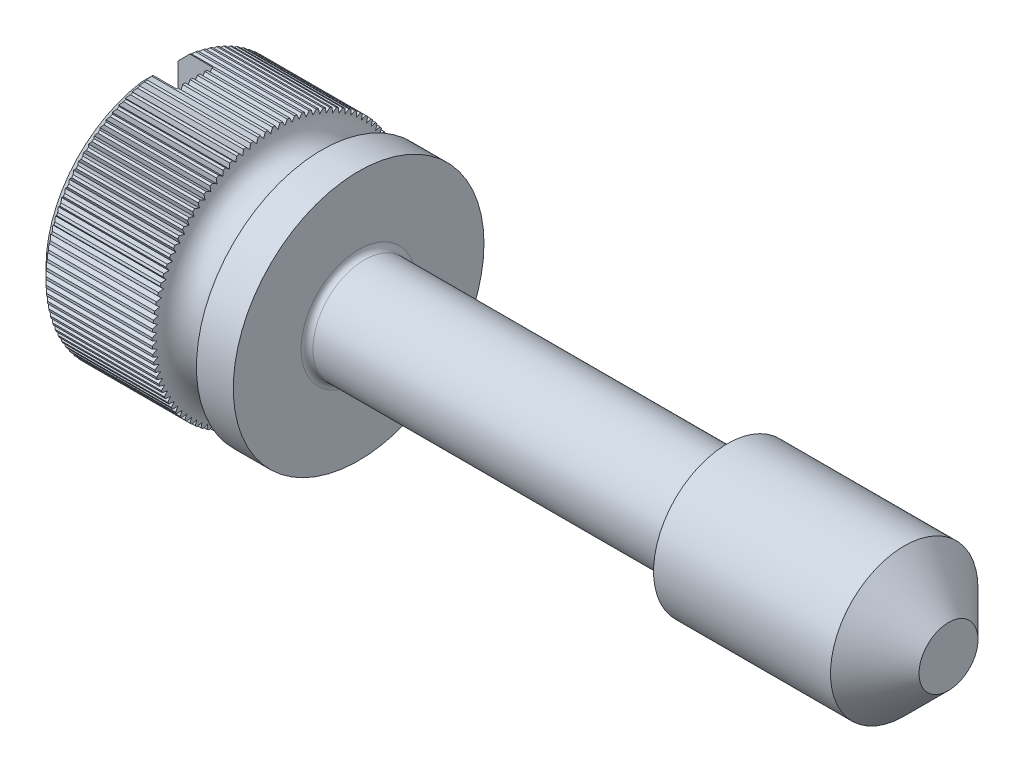
SolidWorks part; units mm, degrees
ref_plane "Front" through (0, 0, 0) normal (0, 0, 1) x (1, 0, 0)
ref_plane "Top" through (0, 0, 0) normal (0, 1, 0) x (1, 0, 0)
ref_plane "Right" through (0, 0, 0) normal (1, 0, 0) x (0, 0, -1)
sketch "Sketch1" plane through (0, 0, 0) normal (1, 0, 0) x (0, 0, -1)
  circle A0 centre (0, 0) radius 8.5
extrude "BaseHead" add sketch "Sketch1" along normal blind 13.5
sketch "Sketch2" plane through (12.6635, 0, 1.1635) normal (0, 1, 0) x (0, 0, 1)
  line L0 (7.3365, -1.6635) -> (10.3365, -1.6635)
  line L1 (7.3365, -4.6635) -> (10.3365, -4.6635)
  line L2 (10.3365, -4.6635) -> (10.3365, -1.6635)
  line L3 (7.3365, -12.6635) -> (7.3365, 0.8365) construction
  line L4 (7.3365, 0.8365) -> (-9.6635, 0.8365) construction
  line L5 (-1.1635, 4.9919) -> (-1.1635, -18.8189) construction
  arc A0 (7.3365, -1.6635) -> (7.3365, -4.6635) centre (7.3365, -3.1635) ccw
  dimension "db" = 3
  dimension "h" = 2.5
  dimension "D3" = 3
revolve "Cut-Revolve1" cut sketch "Sketch2" angle 360 about L5
chamfer "Chamfer1" distance 0.8 angle 45 1 edges at (0, 0, -8.5)
sketch "Sketch3" plane through (0, 0, 0) normal (1, 0, 0) x (0, 0, -1)
  line L1 (0, 8.2113) -> (0.25, 8.6443)
  line L2 (0.25, 8.6443) -> (-0.25, 8.6443)
  line L3 (-0.25, 8.6443) -> (0, 8.2113)
  circle A0 centre (0, 8.5) radius 0.1443 construction
  circle A2 centre (0, 0) radius 8.5 construction
  dimension "D1" = 0.5
extrude "Cut-Extrude1" cut sketch "Sketch3" along normal up to next
pattern_circular "CircularPattern1" count 107 over 360 about axis through (17.6554, 0, 0) along (-1, 0, 0) of "Cut-Extrude1"
sketch "Sketch4" plane through (13.5, 4.4852, -2.1504) normal (1, 0, 0) x (0, 0, -1)
  circle A0 centre (-2.1504, -4.4852) radius 3.5
  circle A1 centre (-2.1504, -4.4852) radius 8.5 construction
  dimension "d1" = 7
extrude "BaseBody" add sketch "Sketch4" along normal blind 40
sketch "Sketch5" plane through (53.5, -0.8575, -1.49) normal (1, 0, 0) x (0, 0, -1)
  circle A0 centre (-1.49, 0.8575) radius 5
  circle A1 centre (-1.49, 0.8575) radius 3.5 construction
extrude "BaseEnd" add sketch "Sketch5" against normal blind 15
cosmetic thread "ThreadCosmetic1" [suppressed] parameters "THD_MINOR"=7.5
chamfer "Chamfer2" distance 3 angle 45 1 edges at (53.5, 0, -5)
fillet "Fillet1" radius 0.4 2 edges at (38.5, 0, -3.5) (13.5, 0, -3.5)
sketch "Sketch6" plane through (-10.163, 0, -10.163) normal (0, 1, 0) x (0, 0, 1)
  line L0 (2.463, 10.163) -> (17.863, 10.163) construction
  line L1 (8.913, 12.563) -> (11.413, 12.563)
  line L2 (8.913, 12.563) -> (8.913, 5.163)
  line L3 (8.913, 5.163) -> (11.413, 5.163)
  line L4 (11.413, 12.563) -> (11.413, 5.163)
  line L5 (10.163, 42.947) -> (10.163, -22.621) construction
  dimension "n" = 2.5
  dimension "t" = 2.4
  dimension "D3" = 5
extrude "Cut-Extrude2" cut sketch "Sketch6" against normal through all and the other way through all
sketch "Sketch7" plane through (0, 0, 0) normal (0, 0, 1) x (1, 0, 0)
  line L0 (38.5, 3.9175) -> (39.125, 5)
  line L1 (39.125, 5) -> (39.125, 6.25)
  line L2 (39.125, 6.25) -> (37.875, 6.25)
  line L3 (37.875, 6.25) -> (37.875, 5)
  line L4 (37.875, 5) -> (38.5, 3.9175)
  line L5 (38.5, 5) -> (38.5, -5) construction
  line L6 (0, 0) -> (41.5302, 0) construction
  dimension "D1" = 10
  dimension "D2" = 1.25
revolve "Cut-Revolve10" [suppressed] cut sketch "Sketch7" angle 360 about L6
pattern_linear "LPattern10" [suppressed] count 10 spacing 1.5 along (1, 0, 0) of bodies 108
equation "\"D1@CircularPattern1\" =  int( \"dk@Sketch1\" * PI / 0.5 + 1  ) "
equation "\"D1@Sketch7\" = \"d@Sketch5\""
equation "\"D2@Sketch7\" =  ( \"d@Sketch5\" - \"THD_MINOR@ThreadCosmetic1\" )  / 2"
equation "\"D3@LPattern10\" = \"D2@Sketch7\" * 1.2"
equation "\"D1@LPattern10\" = \"b@BaseEnd\" / \"D3@LPattern10\""
